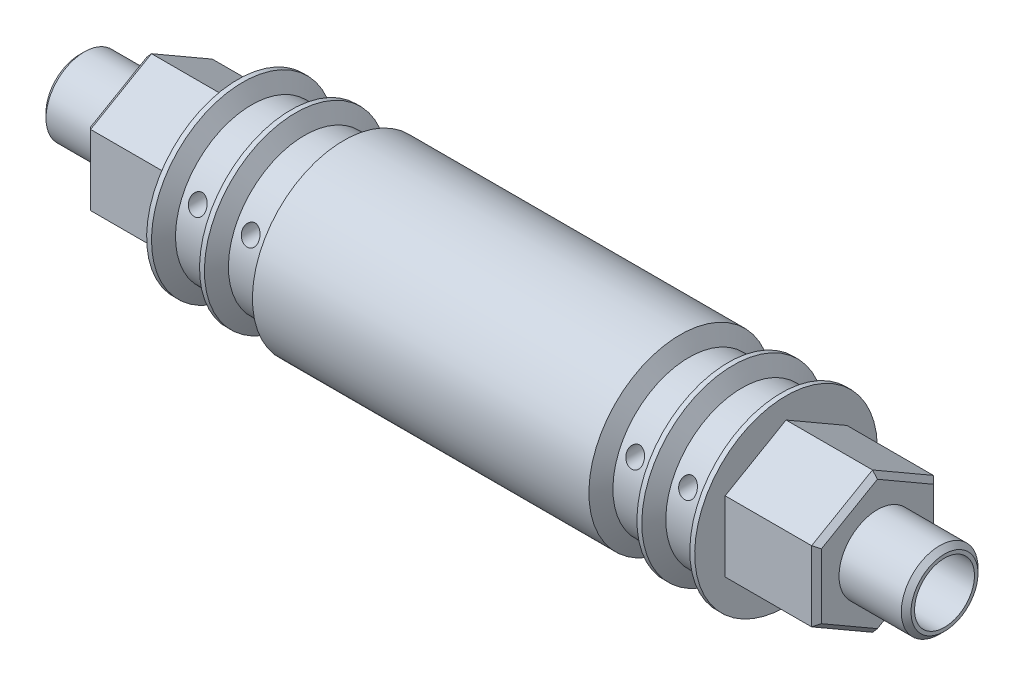
SolidWorks part; units mm, degrees
ref_plane "Front Plane" through (0, 0, 0) normal (0, 0, 1) x (1, 0, 0)
ref_plane "Top Plane" through (0, 0, 0) normal (0, 1, 0) x (1, 0, 0)
ref_plane "Right Plane" through (0, 0, 0) normal (1, 0, 0) x (0, 0, -1)
sketch "Sketch1" plane through (0, 0, 0) normal (0, 0, 1) x (1, 0, 0)
  line L0 (-38.1, 0) -> (38.1, 0) construction
  line L1 (-28.067, 9.525) -> (-27.1505, 7.9375)
  line L2 (-27.1505, 7.9375) -> (-23.9755, 7.9375)
  line L3 (-23.9755, 7.9375) -> (-23.0589, 9.525)
  line L4 (-23.0589, 9.525) -> (-22.5509, 9.525)
  line L5 (-22.5509, 9.525) -> (-21.6344, 7.9375)
  line L6 (-21.6344, 7.9375) -> (-18.4594, 7.9375)
  line L7 (-18.4594, 7.9375) -> (-17.5428, 9.525)
  line L8 (0, 0) -> (0, 25.6809) construction
  line L9 (-17.5428, 9.525) -> (0, 9.525)
  line L10 (-22.8049, 9.525) -> (-22.8049, 0) construction
  line L11 (-28.575, 9.525) -> (-28.575, 4.254)
  line L12 (-28.575, 4.254) -> (-38.1, 4.254)
  line L13 (-38.1, 4.254) -> (-38.1, 4)
  line L14 (-38.1, 0) -> (-28.575, 0)
  line L15 (-28.575, 0) -> (0, 0)
  line L16 (-28.067, 9.525) -> (-28.575, 9.525)
  line L17 (0, 0) -> (0, 9.525)
  line L18 (-38.1, 0) -> (-38.1, -4) construction
  line L19 (-28.575, 4.254) -> (-28.575, 0) construction
  line L20 (-45.1, 4) -> (-45.1, 0)
  line L21 (-45.1, 4) -> (-38.1, 4)
  line L22 (-45.1, 0) -> (-45.1, -4) construction
  line L23 (-38.1, 4) -> (-38.1, 0) construction
  line L24 (-38.1, 0) -> (-45.1, 0)
  line L25 (-45.1, 1.6) -> (-35.275, 1.6)
  line L26 (-35.275, 1.6) -> (-33.675, 0)
  line L27 (-45.1, 1.6) -> (-45.1, -1.6) construction
  line L28 (-48.275, -1.5) -> (-35.275, -1.5) construction
  line L29 (-48.275, -1.5) -> (-48.275, 1.5) construction
  line L30 (-48.275, 1.5) -> (-35.275, 1.5) construction
  line L31 (-35.275, -1.5) -> (-35.275, 1.5) construction
  line L32 (-48.275, -1.5) -> (-35.275, 1.5) construction
  line L33 (-48.275, 1.5) -> (-35.275, -1.5) construction
  point P27 (-41.775, 0)
  point P40 (-45.1, 0)
  dimension "D2" = 3.175
  dimension "D3" = 1.5875
  dimension "D4" = 60
  dimension "D6" = 1.5875
  dimension "D5" = 0.508
  dimension "D7" = 1.5875
  dimension "D8" = 0.508
  dimension "D11" = 9.525
  dimension "D12" = 8
  dimension "D13" = 7
  dimension "D10" = 0.254
  dimension "D9" = 76.2
  dimension "D14" = 9.525
  dimension "D15" = 13
  dimension "D16" = 3
  dimension "D17" = 3.175
  dimension "D18" = 45
  dimension "D19" = 3.2
revolve "Revolve1" add sketch "Sketch1" angle 360 about L0 region at (-17.4824, 4.2193, 0)
sketch "Sketch4" plane through (-28.575, 0, 0) normal (-1, 0, 0) x (0, 0, 1)
  line L1 (0, 7.3323) -> (-6.35, 3.6662)
  line L2 (-6.35, 3.6662) -> (-6.35, -3.6662)
  line L3 (-6.35, -3.6662) -> (0, -7.3323)
  line L4 (0, -7.3323) -> (6.35, -3.6662)
  line L5 (6.35, -3.6662) -> (6.35, 3.6662)
  line L6 (6.35, 3.6662) -> (0, 7.3323)
  circle A0 centre (0, 0) radius 6.35 construction
  dimension "D1" = 12.7
extrude "Boss-Extrude4" add sketch "Sketch4" along normal up to surface (9.525 mm away) up to face at (-38.1, -4, 0)
sketch "Sketch6" plane through (0, 0, 0) normal (0, 0, 1) x (1, 0, 0)
  line L0 (-25.563, 7.9375) -> (-25.563, 3.302) construction
  line L1 (-27.1505, 7.9375) -> (-23.9755, 7.9375) construction
  line L2 (-20.0469, 7.9375) -> (-20.0469, 3.302) construction
  line L3 (-21.6344, 7.9375) -> (-18.4594, 7.9375) construction
  circle A0 centre (-25.563, 3.302) radius 0.889
  circle A1 centre (-20.0469, 3.302) radius 0.889
  dimension "D1" = 1.778
  dimension "D2" = 3.302
extrude "Cut-Extrude1" cut sketch "Sketch6" against normal through all both and the other way through all
chamfer "Chamfer2" distance 0.508 angle 45 6 edges at (-38.1, 5.4993, 3.175) (-38.1, 0, 6.35) (-38.1, -5.4993, 3.175) (-38.1, -5.4993, -3.175) (-38.1, 0, -6.35) (-38.1, 5.4993, -3.175)
chamfer "Chamfer3" distance 0.508 angle 45 1 edges at (-45.1, -4, 0)
mirror "Mirror2" about plane through (0, 0, 0) normal (1, 0, 0) of bodies 107
sketch "Sketch7" plane through (-45.1, 0, 0) normal (-1, 0, 0) x (0, 0, 1)
  circle A0 centre (0, 0) radius 3.125
  dimension "D1" = 6.25
extrude "Cut-Extrude2" cut sketch "Sketch7" against normal through all
equation "\"D12@Sketch1\"=8mm"
equation "\"D19@Sketch1\"=3.2mm"
equation "\"D1@Sketch7\"=6mm+.25mm"
